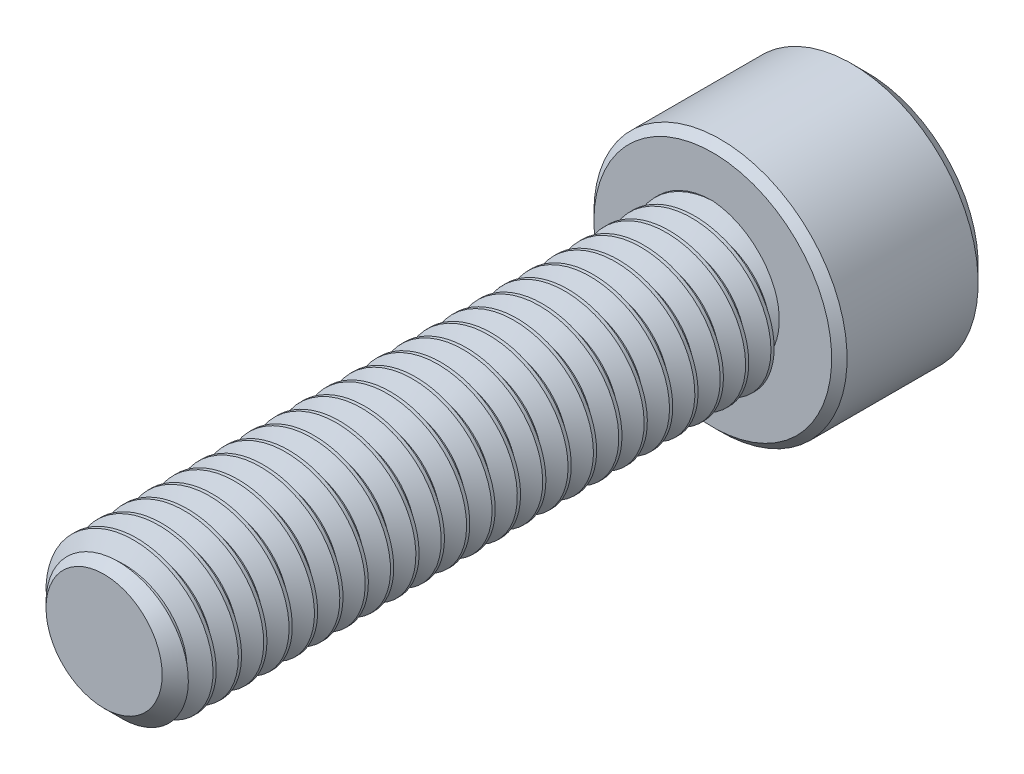
SolidWorks part; units mm, degrees
material "1023 Carbon Steel Sheet (SS)"
ref_plane "Front Plane" through (0, 0, 0) normal (0, 0, 1) x (1, 0, 0)
ref_plane "Top Plane" through (0, 0, 0) normal (0, 1, 0) x (1, 0, 0)
ref_plane "Right Plane" through (0, 0, 0) normal (1, 0, 0) x (0, 0, -1)
sketch "Sketch1" plane through (0, 0, 0) normal (0, 0, 1) x (1, 0, 0)
  line L0 (0, 2.413) -> (0, -2.413) construction
  circle A0 centre (0, 0) radius 2.413
  dimension "OD" = 4.826
extrude "Extrude1" add sketch "Sketch1" against normal blind 19.05
sketch "Sketch2" plane through (0, 0, 0) normal (0, 0, 1) x (1, 0, 0)
  circle A0 centre (0, 0) radius 2.413 construction
  circle A1 centre (0, 0) radius 2.413
curve "Helix/Spiral1" pitch 0.7937 height 19.8438 turns 25 parameters "pitch"=0.7937
chamfer "Chamfer3" distance 0.5953 angle 45 1 edges at (2.413, 0, 0)
sketch "Sketch3" plane through (0, 0, 0) normal (1, 0, 0) x (0, 0, -1)
  line L0 (-0.6945, 2.413) -> (-0.3969, 1.8974)
  line L1 (-0.3969, 1.8974) -> (-0.2977, 1.8974)
  line L2 (-0.2977, 1.8974) -> (0, 2.413)
  line L3 (-0.6945, 2.413) -> (0, 2.413)
  line L4 (-0.3473, 2.413) -> (-0.3473, 1.8974) construction
  line L5 (-0.5457, 2.1552) -> (-0.1488, 2.1552) construction
  line L6 (0, 2.413) -> (0, -2.413) construction
  dimension "D1" = 0.0992
  dimension "D2" = 0.3969
  dimension "D3" = 60
sweep "Cut-Sweep1" cut profiles "Sketch3" path "Helix/Spiral1"
sketch "Sketch6" plane through (0, 0, -19.05) normal (0, 0, -1) x (-1, 0, 0)
  circle A0 centre (0, 0) radius 3.9624
  dimension "head dia" = 7.9248
extrude "Extrude2" add sketch "Sketch6" along normal blind 4.826
sketch "Sketch7" plane through (0, 0, -23.876) normal (0, 0, -1) x (-1, 0, 0)
  line L1 (0, 2.2914) -> (-1.9844, 1.1457)
  line L2 (-1.9844, 1.1457) -> (-1.9844, -1.1457)
  line L3 (-1.9844, -1.1457) -> (0, -2.2914)
  line L4 (0, -2.2914) -> (1.9844, -1.1457)
  line L5 (1.9844, -1.1457) -> (1.9844, 1.1457)
  line L6 (1.9844, 1.1457) -> (0, 2.2914)
  circle A0 centre (0, 0) radius 1.9844 construction
  dimension "hex dia" = 3.9688
extrude "Cut-Extrude1" cut sketch "Sketch7" against normal blind 2.9766
sketch "Sketch8" plane through (0, 0, -23.876) normal (0, 0, -1) x (-1, 0, 0)
  circle A0 centre (0, 0) radius 2.2914
extrude "Cut-Extrude2" cut sketch "Sketch8" against normal blind 0.4826 draft 45
chamfer "Chamfer1" distance 0.4826 angle 45 1 edges at (-3.9624, 0, -23.876)
chamfer "Chamfer2" distance 0.2413 angle 45 1 edges at (-3.9624, 0, -19.05)
sketch "Sketch9" plane through (0, 0, 0) normal (1, 0, 0) x (0, 0, -1)
  line L0 (0, 2.413) -> (0, -2.413) construction
  line L1 (4.3656, 2.413) -> (4.3656, -2.413) construction
  line L2 (19.05, 3.9624) -> (19.05, -3.9624) construction
  line L3 (23.876, 3.9624) -> (23.876, -3.9624) construction
  line L4 (23.876, 0) -> (0, 0) construction
  dimension "D1" = 4.3656
  dimension "D2" = 4.826
  dimension "D3" = 7.9248
  dimension "D4" = 19.05
equation "\"D3@Helix/Spiral1\" = \"screw length@Extrude1\"+\"pitch@Helix/Spiral1\""
equation "\"D1@Sketch3\" = \"pitch@Helix/Spiral1\"*.125"
equation "\"D2@Sketch3\" = \"pitch@Helix/Spiral1\"*.5"
equation "\"D1@Cut-Extrude1\" = \"hex dia@Sketch7\"*.75"
equation "\"D1@Chamfer1\" = \"head depth@Extrude2\"/10"
equation "\"D1@Sketch9\" = \"pitch@Helix/Spiral1\"*5.5"
equation "\"D1@Chamfer2\" = \"D1@Chamfer1\"/2"
equation "\"D1@Cut-Extrude2\" = \"D1@Chamfer2\"*2"
equation "\"D1@Chamfer3\" = \"pitch@Helix/Spiral1\"*.750"
equation "\"D2@Sketch9\" = \"head depth@Extrude2\""
equation "\"D3@Sketch9\" = \"head dia@Sketch6\""
equation "\"D4@Sketch9\" = \"screw length@Extrude1\""
